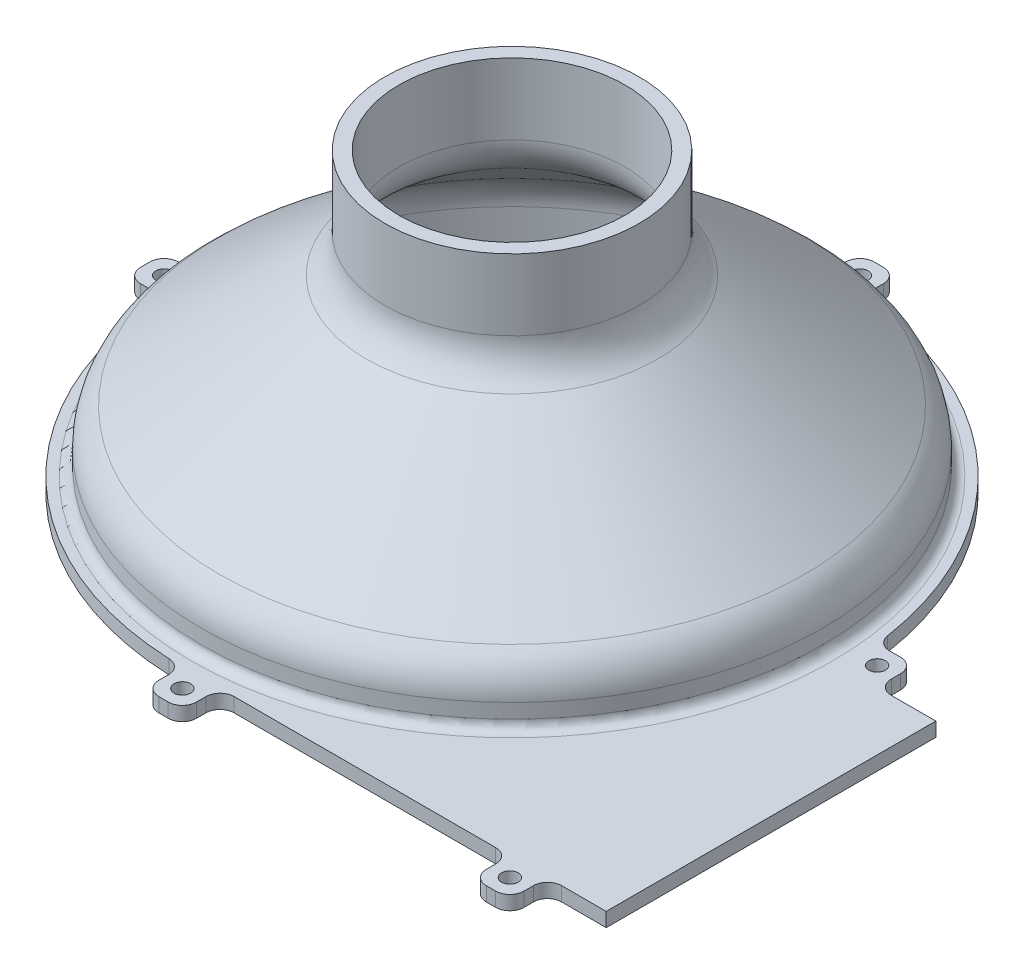
SolidWorks part; units mm, degrees
ref_plane "Front Plane" through (0, 0, 0) normal (0, 0, 1) x (1, 0, 0)
ref_plane "Top Plane" through (0, 0, 0) normal (0, 1, 0) x (1, 0, 0)
ref_plane "Right Plane" through (0, 0, 0) normal (1, 0, 0) x (0, 0, -1)
sketch "Sketch2" plane through (0, 0, 0) normal (0, 1, 0) x (1, 0, 0)
  line L0 (70, 0) -> (70, -70) construction
  line L1 (0, -70) -> (90, -70)
  line L3 (70, 0) -> (90, 0)
  line L4 (90, -70) -> (90, 0)
  arc A0 (70, 0) -> (0, -70) centre (0, 0) ccw
  circle A1 centre (0, 0) radius 63
  dimension "D1" = 140
  dimension "D4" = 126
  dimension "D3" = 20
extrude "Boss-Extrude1" add sketch "Sketch2" along normal blind 3
sketch "Sketch3" plane through (0, 3, 0) normal (0, 1, 0) x (1, 0, 0)
  circle A2 centre (0, 0) radius 63 construction
  circle A3 centre (0, 0) radius 63
  circle A4 centre (0, 0) radius 66
  dimension "D1" = 3
extrude "Boss-Extrude2" add sketch "Sketch3" along normal blind 10
sketch "Sketch6" plane through (0, 0, 0) normal (1, 0, 0) x (0, 0, -1)
  line L0 (-66, 13) -> (-27, 43)
  line L1 (-27, 43) -> (-24, 43)
  line L2 (-24, 43) -> (-63, 13)
  line L3 (66, 13) -> (-66, 13) construction
  line L4 (-66, 13) -> (-63, 13)
  line L5 (0, 0) -> (0, 43) construction
  line L6 (-70, 0) -> (70, 0) construction
  line L7 (-24, 43) -> (0, 43) construction
  dimension "D1" = 3
  dimension "D2" = 30
  dimension "D3" = 27
revolve "Revolve1" add sketch "Sketch6" angle 360 about L5
sketch "Sketch7" plane through (0, 43, 0) normal (0, 1, 0) x (1, 0, 0)
  circle A0 centre (0, 0) radius 27
  circle A1 centre (0, 0) radius 24
  circle A2 centre (0, 0) radius 24 construction
  circle A3 centre (0, 0) radius 27 construction
extrude "Boss-Extrude3" add sketch "Sketch7" along normal blind 20
fillet "Fillet1" radius 10 4 edges at (0, 43, -24) (0, 13, -63) (0, 13, 66) (0, 43, 27)
fillet "Fillet2" radius 2 1 edges at (0, 3, 66)
sketch "Sketch8" plane through (0, 0, 0) normal (0, -1, 0) x (1, 0, 0)
  line L21 (90, 0) -> (70, 0) construction
  line L22 (77.5414, 0) -> (69.5414, 0)
  line L23 (77.5414, 0) -> (77.5414, -8)
  line L24 (77.5414, -8) -> (69.5414, -8)
  line L25 (69.5414, 0) -> (69.5414, -8)
  line L26 (73.5414, 0) -> (73.5414, -8) construction
  line L27 (0, 70) -> (90, 70) construction
  line L28 (77.5414, 70) -> (69.5414, 70)
  line L29 (77.5414, 70) -> (77.5414, 78)
  line L30 (77.5414, 78) -> (69.5414, 78)
  line L31 (69.5414, 70) -> (69.5414, 78)
  line L32 (73.5414, 78) -> (73.5414, 70) construction
  line L33 (-73.8856, 4) -> (-73.8856, -4) construction
  line L34 (-69.8856, 4) -> (-77.8856, 4)
  line L35 (-69.8856, 4) -> (-69.8856, -4)
  line L36 (-69.8856, -4) -> (-77.8856, -4)
  line L37 (-77.8856, 4) -> (-77.8856, -4)
  line L38 (0, -69.8856) -> (0, -77.8856) construction
  line L39 (-4, -69.8856) -> (4, -69.8856)
  line L40 (-4, -69.8856) -> (-4, -77.8856)
  line L41 (-4, -77.8856) -> (4, -77.8856)
  line L42 (4, -69.8856) -> (4, -77.8856)
  line L43 (4, 78) -> (4, 70) construction
  line L44 (0, 70) -> (8, 70)
  line L45 (0, 70) -> (0, 78)
  line L46 (0, 78) -> (8, 78)
  line L47 (8, 70) -> (8, 78)
  arc A23 (0, 70) -> (70, 0) centre (0, 0) ccw construction
  circle A24 centre (73.5414, -4) radius 1.75
  circle A25 centre (73.5414, 74) radius 1.75
  circle A26 centre (-73.8856, 0) radius 1.75
  circle A27 centre (0, -73.8856) radius 1.75
  circle A28 centre (4, 74) radius 1.75
  dimension "D3" = 3.5
  dimension "D5" = 3.5
  dimension "D8" = 3.5
  dimension "D11" = 3.5
  dimension "D13" = 3.5
  dimension "D1" = 8
  dimension "D2" = 8
  dimension "D4" = 8
  dimension "D6" = 8
  dimension "D7" = 8
  dimension "D9" = 8
  dimension "D10" = 8
  dimension "D12" = 8
extrude "Boss-Extrude4" add sketch "Sketch8" against normal up to surface (3 mm away) up to face at (0, 3, 68)
fillet "Fillet3" radius 3 19 edges at (77.5414, 1.5, 0) (69.5414, 1.5, -8) (77.5414, 1.5, -8) (77.5414, 1.5, 70) (77.5414, 1.5, 78) (69.5414, 1.5, 78) (69.5414, 1.5, 70) (8, 1.5, 70) (8, 1.5, 78) (0, 1.5, 78) (0, 1.5, 70) (-69.8856, 1.5, 4) (-77.8856, 1.5, 4) (-77.8856, 1.5, -4) (-69.8856, 1.5, -4) (-4, 1.5, -77.8856) (4, 1.5, -77.8856) (4, 1.5, -69.8856) (-4, 1.5, -69.8856)
equation "\"LoftHeight\"= 30"
